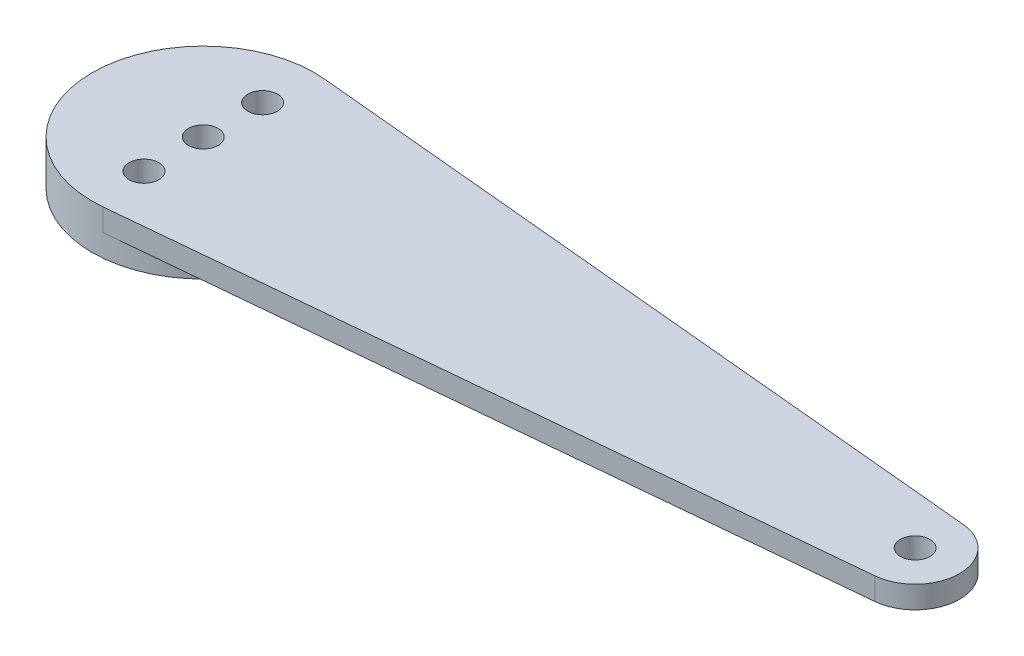
SolidWorks part; units mm, degrees
ref_plane "Front" through (0, 0, 0) normal (0, 0, 1) x (1, 0, 0)
ref_plane "Top" through (0, 0, 0) normal (0, 1, 0) x (1, 0, 0)
ref_plane "Right" through (0, 0, 0) normal (1, 0, 0) x (0, 0, -1)
sketch "Sketch1" plane through (0, 0, 0) normal (0, 1, 0) x (1, 0, 0)
  line L0 (0.5625, 5.9736) -> (-94.5938, 14.9339)
  line L3 (0.5625, -5.9736) -> (-94.5938, -14.9339)
  line L4 (-96, 0) -> (-96, 8) construction
  circle A3 centre (0, 0) radius 2
  arc A4 (0.5625, 5.9736) -> (0.5625, -5.9736) centre (0, 0) cw
  circle A5 centre (-96, 0) radius 15
  circle A6 centre (-96, 0) radius 2
  circle A7 centre (-96, 8) radius 2
  circle A8 centre (-96, -8) radius 2
  point P4 (-83.635, -9.3602)
  point P9 (-92.0698, 6.9681)
  point P12 (-82.9295, -8.734)
  point P13 (0, 0)
  point P18 (0, 0)
  dimension "D1" = 4
  dimension "D2" = 30
  dimension "D3" = 4
  dimension "D7" = 4
  dimension "D4" = 8
  dimension "D6" = 96
  dimension "D5" = 2
extrude "Boss-Extrude1" add sketch "Sketch1" along normal blind 3 contours A5 L3 A4 L0 A3 | A5 A8 A6 A7 region at (-46.1998, 0, 0) region at (-85.2211, 0, -9.8116)
extrude "Boss-Extrude2" add sketch "Sketch1<3>" against normal blind 3 contours A5 A8 A6 A7 region at (-85.2211, 0, -9.8116)
sketch "Sketch1<3>" plane through (0, 0, 0) normal (0, 1, 0) x (1, 0, 0) same geometry as "Sketch1"
